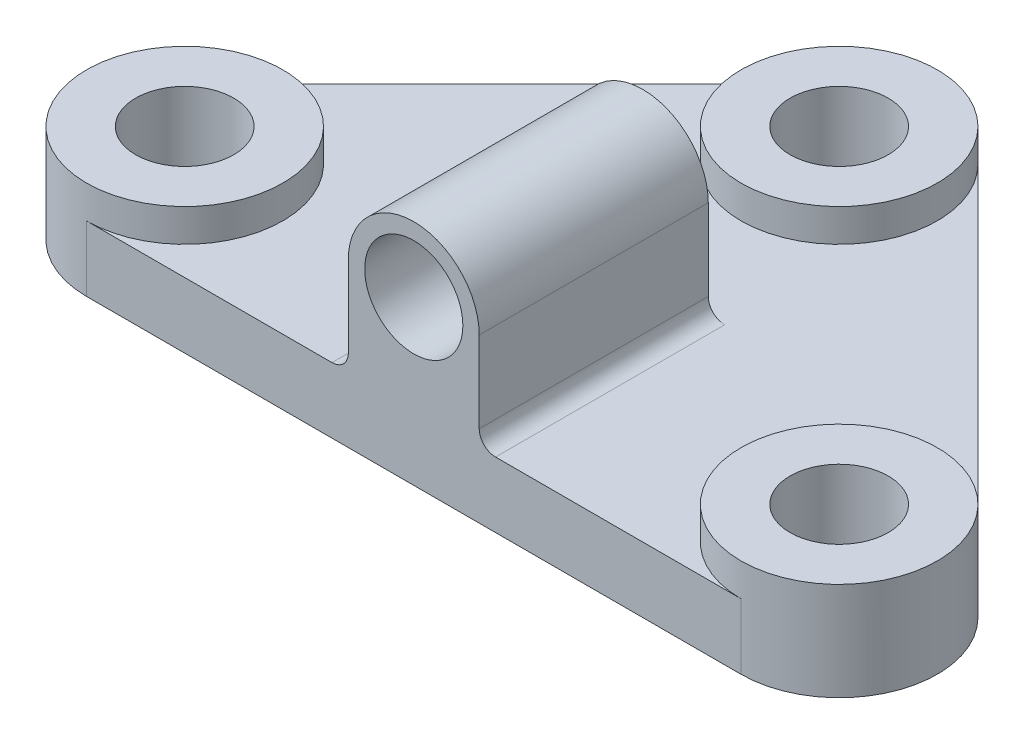
SolidWorks part; units mm, degrees
ref_plane "Front Plane" through (0, 0, 0) normal (0, 0, 1) x (1, 0, 0)
ref_plane "Top Plane" through (0, 0, 0) normal (0, 1, 0) x (1, 0, 0)
ref_plane "Right Plane" through (0, 0, 0) normal (1, 0, 0) x (0, 0, -1)
sketch "Sketch1" plane through (0, 0, 0) normal (0, 1, 0) x (1, 0, 0)
  line L0 (-21.2132, 21.2132) -> (78.7868, 121.2132)
  line L1 (0, -30) -> (200, -30)
  line L2 (221.2132, 21.2132) -> (121.2132, 121.2132)
  line L4 (80, -30) -> (120, -30)
  line L5 (80, -30) -> (80, 40)
  line L6 (80, 40) -> (120, 40)
  line L7 (120, -30) -> (120, 40)
  circle A0 centre (0, 0) radius 30
  circle A1 centre (100, 100) radius 30
  circle A2 centre (200, 0) radius 30
  circle A3 centre (0, 0) radius 15
  circle A4 centre (100, 100) radius 15
  circle A5 centre (200, 0) radius 15
  dimension "D1" = 200
  dimension "D3" = 100
  dimension "D4" = 60
  dimension "D5" = 30
  dimension "D2" = 100
  dimension "D6" = 40
  dimension "D7" = 70
  dimension "D8" = 20
extrude "Boss-Extrude1" add sketch "Sketch1" along normal blind 20 contours A2 L2 A1 L0 A0 L1 L5 L6 L7 region at (30.8071, 0, -69.1929)
extrude "Boss-Extrude2" add sketch "Sketch1<3>" along normal blind 30 contours A0 A3 | A1 A4 | A2 A5 region at (11.1558, 0, -26.9324) region at (100, 0, -129.1515) region at (226.9324, 0, -11.1558)
sketch "Sketch1<3>" plane through (0, 0, 0) normal (0, 1, 0) x (1, 0, 0) same geometry as "Sketch1"
extrude "Boss-Extrude3" add sketch "Sketch1<4>" along normal blind 69.8 contours L1 L7 L6 L5 region at (100, 0, -5)
sketch "Sketch1<4>" plane through (0, 0, 0) normal (0, 1, 0) x (1, 0, 0) same geometry as "Sketch1"
fillet "Fillet1" 2 edges at (120, 69.8, -5) (80, 69.8, -5) type full round first side face at (120, 44.9, -5) second side face at (80, 44.9, -5) middle face at (100, 69.8, -5)
fillet "Fillet2" radius 5 2 edges at (120, 20, -5) (80, 20, -5)
sketch "Sketch2" plane through (0, 0, 30) normal (0, 0, 1) x (1, 0, 0)
  circle A0 centre (100, 49.8) radius 15
  arc A1 (120, 49.8) -> (80, 49.8) centre (100, 49.8) ccw construction
  arc A2 (120, 49.8) -> (80, 49.8) centre (100, 49.8) ccw construction
  dimension "D1" = 30
extrude "Cut-Extrude1" cut sketch "Sketch2" against normal up to next
